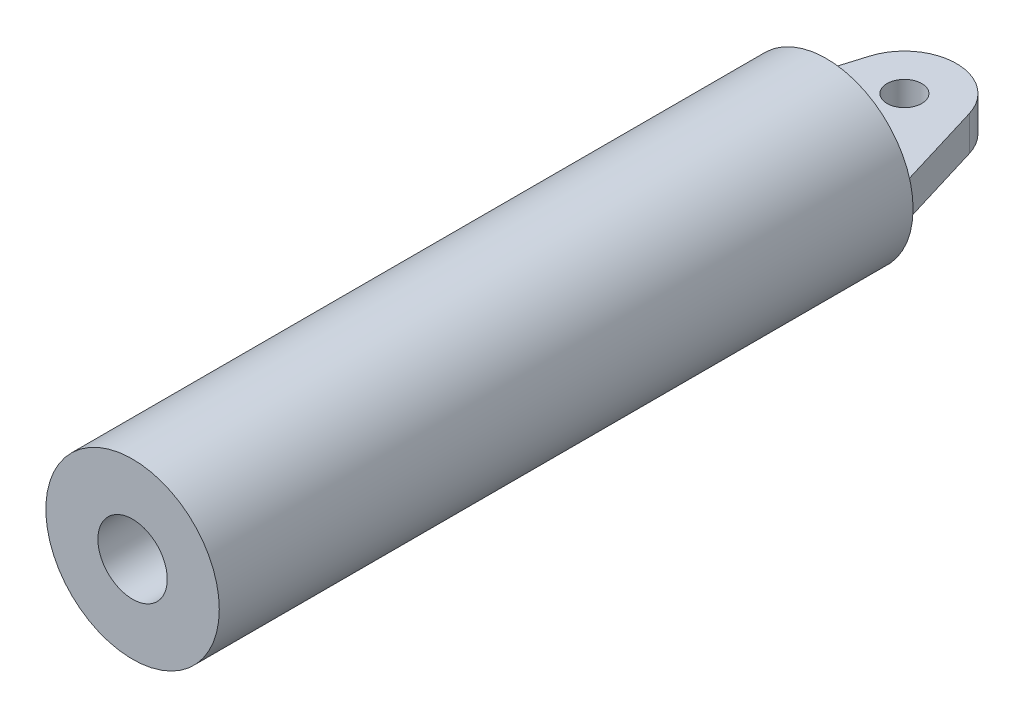
SolidWorks part; units mm, degrees
ref_plane "Front Plane" through (0, 0, 0) normal (0, 0, 1) x (1, 0, 0)
ref_plane "Top Plane" through (0, 0, 0) normal (0, 1, 0) x (1, 0, 0)
ref_plane "Right Plane" through (0, 0, 0) normal (1, 0, 0) x (0, 0, -1)
sketch "Sketch1" plane through (0, 0, 0) normal (0, 0, 1) x (1, 0, 0)
  circle A0 centre (0, 0) radius 50
  dimension "D1" = 100
extrude "Boss-Extrude1" add sketch "Sketch1" along normal blind 400
sketch "Sketch2" plane through (0, 0, 0) normal (0, 1, 0) x (1, 0, 0)
  line L0 (-45, 0) -> (-28.7083, 53.7083)
  line L1 (50, 0) -> (-50, 0) construction
  line L2 (28.7083, 53.7083) -> (45, 0)
  line L3 (-45, 0) -> (45, 0)
  circle A0 centre (0, 45) radius 10
  arc A1 (-28.7083, 53.7083) -> (28.7083, 53.7083) centre (0, 45) cw
  dimension "D1" = 30
  dimension "D2" = 20
  dimension "D3" = 45
  dimension "D4" = 45
extrude "Boss-Extrude2" add sketch "Sketch2" along normal mid plane 20
shell "Shell1" thickness 30 removed face at (50, 0, 400)
